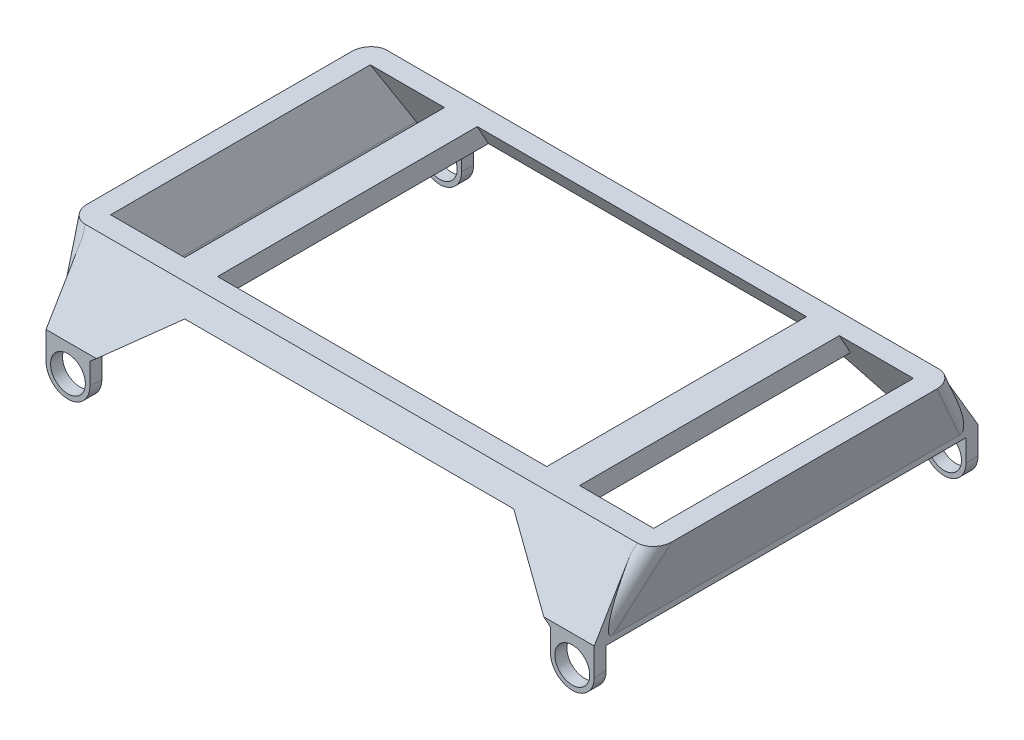
SolidWorks part; units mm, degrees
ref_plane "Front Plane" through (0, 0, 0) normal (0, 0, 1) x (1, 0, 0)
ref_plane "Top Plane" through (0, 0, 0) normal (0, 1, 0) x (1, 0, 0)
ref_plane "Right Plane" through (0, 0, 0) normal (1, 0, 0) x (0, 0, -1)
sketch "Sketch1" plane through (0, 0, 0) normal (0, 1, 0) x (1, 0, 0)
  line L1 (-50, -35) -> (50, -35)
  line L2 (-50, -35) -> (-50, 35)
  line L3 (-50, 35) -> (50, 35)
  line L4 (50, -35) -> (50, 35)
  line L5 (-50, -35) -> (50, 35) construction
  line L6 (-50, 35) -> (50, -35) construction
  point P0 (0, 0)
  dimension "D1" = 100
  dimension "D2" = 70
extrude "Boss-Extrude1" add sketch "Sketch1" along normal blind 1
ref_plane "Plane6" through (0, 16, 0) normal (0, 1, 0) x (1, 0, 0)
ref_plane "Plane1" through (0, 13.7, 0) normal (0, 1, 0) x (1, 0, 0)
sketch "Sketch2" plane through (0, 13.7, 0) normal (0, 1, 0) x (1, 0, 0)
  line L1 (-53.34, -27.5) -> (53.34, -27.5)
  line L2 (-53.34, -27.5) -> (-53.34, 27.5)
  line L3 (-53.34, 27.5) -> (53.34, 27.5)
  line L4 (53.34, -27.5) -> (53.34, 27.5)
  line L5 (-53.34, -27.5) -> (53.34, 27.5) construction
  line L6 (-53.34, 27.5) -> (53.34, -27.5) construction
  point P0 (0, 0)
  dimension "D1" = 106.68
  dimension "D2" = 55
loft "Loft1" add profiles "Sketch2" section face at (0, 1, 0) section "Sketch2" connector at (-50, 1, 35) connector at (-53.34, 13.7, 27.5)
sketch "Sketch3" plane through (0, 13.7, 0) normal (0, 1, 0) x (1, 0, 0)
  line L20 (49.53, -23.69) -> (49.53, 23.69)
  line L21 (49.53, 23.69) -> (-49.53, 23.69)
  line L22 (-49.53, 23.69) -> (-49.53, -23.69)
  line L23 (-49.53, -23.69) -> (49.53, -23.69)
  line L24 (49.53, -23.69) -> (49.53, 23.69)
  line L25 (49.53, 23.69) -> (-49.53, 23.69)
  line L26 (-49.53, 23.69) -> (-49.53, -23.69)
  line L27 (-49.53, -23.69) -> (49.53, -23.69)
  dimension "D2" = 3.81
sketch "Sketch7" plane through (0, 0, 0) normal (0, -1, 0) x (1, 0, 0)
  line L14 (46.19, -31.19) -> (46.19, 31.19)
  line L15 (46.19, 31.19) -> (-46.19, 31.19)
  line L16 (-46.19, 31.19) -> (-46.19, -31.19)
  line L17 (-46.19, -31.19) -> (46.19, -31.19)
  line L18 (46.19, -31.19) -> (46.19, 31.19)
  line L19 (46.19, 31.19) -> (-46.19, 31.19)
  line L20 (-46.19, 31.19) -> (-46.19, -31.19)
  line L21 (-46.19, -31.19) -> (46.19, -31.19)
  dimension "D1" = 3.81
loft "Cut-Loft2" cut profiles "Sketch3", "Sketch7" connector at (-49.53, 13.7, -23.69) connector at (-46.19, 0, -31.19)
fillet "Fillet3" radius 2.54 8 edges
ref_plane "Plane2" through (0, 0, 12.7) normal (0, 0, 1) x (1, 0, 0)
ref_plane "Plane3" through (0, 0, 0) normal (0, 0, 1) x (1, 0, 0)
sketch "Sketch8" plane through (0, 0, 0) normal (0, -1, 0) x (1, 0, 0)
  line L2 (0, 0) -> (-46, 0) construction
  line L3 (-54.133, 32.6952) -> (-54.133, 35) construction
  line L4 (-49.4236, 32.6952) -> (49.4236, 32.6952) construction
  line L5 (-50, 35) -> (50, 35) construction
  line L6 (-46, 0) -> (-46, 33.9061) construction
  line L8 (-50, 32.8123) -> (-42, 32.8123)
  line L9 (-50, 32.8123) -> (-50, 35)
  line L10 (-50, 35) -> (-42, 35)
  line L11 (-42, 32.8123) -> (-42, 35)
  line L12 (-50, 32.8123) -> (-42, 35) construction
  line L13 (-50, 35) -> (-42, 32.8123) construction
  dimension "D1" = 46
  dimension "D2" = 8
  dimension "D3" = 2.1877
extrude "Boss-Extrude4" add sketch "Sketch8" along normal blind 4
sketch "Sketch11" plane through (0, 0, 32.8123) normal (0, 0, -1) x (-1, 0, 0)
  line L2 (50, -4) -> (42, -4) construction
  line L3 (50, -4) -> (42, -4)
  arc A0 (42, -4) -> (50, -4) centre (46, -4) ccw
extrude "Boss-Extrude5" add sketch "Sketch11" against normal blind 2.1877
ref_plane "Plane5" through (0, 0, 0) normal (1, 0, 0) x (0, 0, -1)
sketch "Sketch14" plane through (0, 0, 32.8123) normal (0, 0, -1) x (-1, 0, 0)
  line L0 (50, 0) -> (42, 0) construction
  line L1 (46, 0) -> (46, -4) construction
  circle A0 centre (46, -4) radius 3.175
extrude "Cut-Extrude2" cut sketch "Sketch14" against normal blind 2.1877
mirror "Mirror4" about plane through (0, 0, 0) normal (0, 0, 1) of "Cut-Extrude2", "Boss-Extrude5", "Boss-Extrude4"
mirror "Mirror5" about plane through (0, 0, 0) normal (1, 0, 0) of "Mirror4", "Cut-Extrude2", "Boss-Extrude5", "Boss-Extrude4"
sketch "Sketch22" plane through (0, 0, 0) normal (0, 0, 1) x (1, 0, 0)
  line L0 (-42, 0) -> (0, 0)
  line L1 (0, 0) -> (0, 10) construction
  line L2 (0, 10) -> (-30, 10) construction
  line L3 (-42, 0) -> (-30, 10)
  line L4 (-30, 10) -> (0, 10)
  line L5 (0, 10) -> (0, 0)
  point P4 (0, 0)
  dimension "D1" = 10
  dimension "D2" = 30
extrude "Cut-Extrude5" cut sketch "Sketch22" against normal through all and the other way through all
mirror "Mirror6" about plane through (0, 0, 0) normal (1, 0, 0) of "Cut-Extrude5"
sketch "Sketch25" plane through (0, 0, 0) normal (0, 0, 1) x (1, 0, 0)
  line L0 (0, 0) -> (0, 11.85) construction
  line L1 (0, 11.85) -> (-33.02, 11.85) construction
  line L3 (-30.02, 10) -> (-36.02, 10)
  line L4 (-30.02, 10) -> (-30.02, 13.7)
  line L5 (-30.02, 13.7) -> (-36.02, 13.7)
  line L6 (-36.02, 10) -> (-36.02, 13.7)
  line L7 (-30.02, 10) -> (-36.02, 13.7) construction
  line L8 (-30.02, 13.7) -> (-36.02, 10) construction
  dimension "D1" = 3.7
  dimension "D2" = 6
  dimension "D3" = 11.85
  dimension "D4" = 33.02
extrude "Boss-Extrude7" add sketch "Sketch25" along normal up to next and the other way up to next
mirror "Mirror7" about plane through (0, 0, 0) normal (1, 0, 0) of "Boss-Extrude7"
